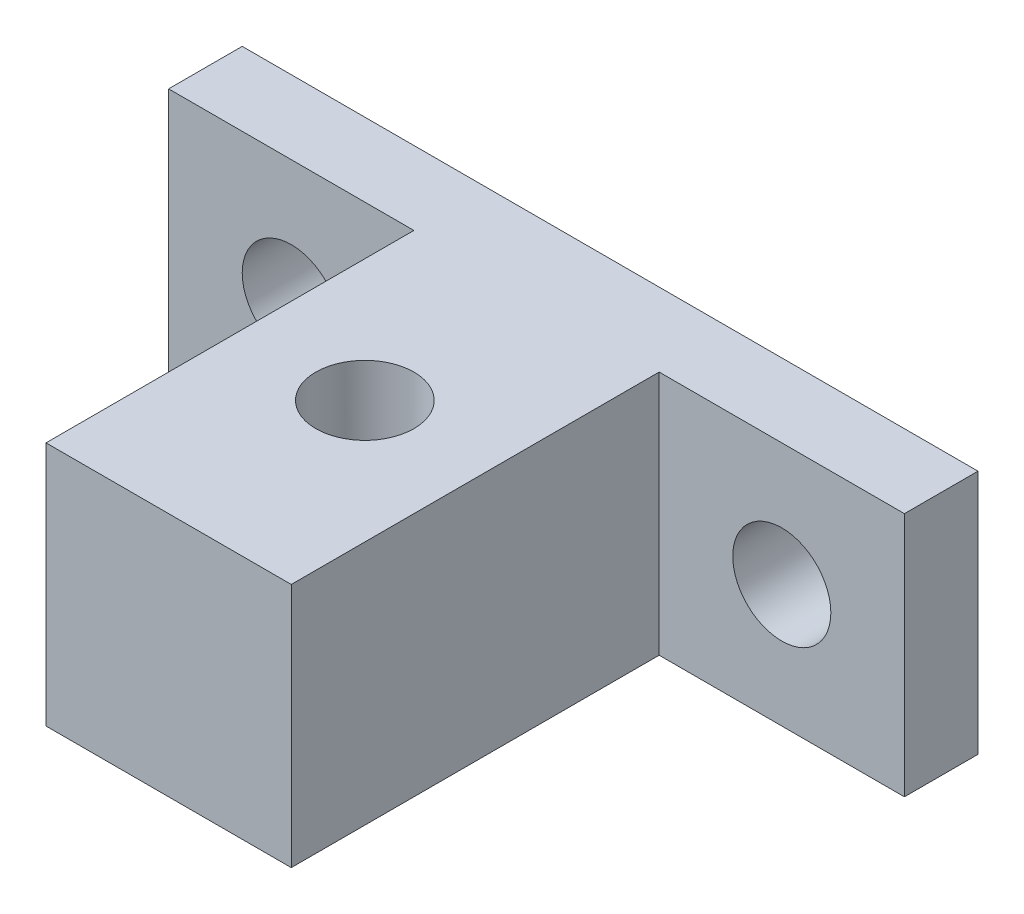
SolidWorks part; units mm, degrees
ref_plane "Front Plane" through (0, 0, 0) normal (0, 0, 1) x (1, 0, 0)
ref_plane "Top Plane" through (0, 0, 0) normal (0, 1, 0) x (1, 0, 0)
ref_plane "Right Plane" through (0, 0, 0) normal (1, 0, 0) x (0, 0, -1)
sketch "Sketch1" plane through (0, 0, 0) normal (0, 0, 1) x (1, 0, 0)
  line L0 (163.3569, -3.3) -> (103.3569, -3.3) construction
  line L1 (25, -3.3) -> (-5, -3.3)
  line L2 (25, -3.3) -> (25, -13.3)
  line L3 (25, -13.3) -> (-5, -13.3)
  line L4 (-5, -3.3) -> (-5, -13.3)
  line L5 (25, -3.3) -> (-5, -13.3) construction
  line L6 (25, -13.3) -> (-5, -3.3) construction
  line L7 (25, -8.3) -> (-5, -8.3) construction
  line L8 (10, -13.3) -> (10, -3.3) construction
  circle A0 centre (20, -8.3) radius 2
  circle A1 centre (0, -8.3) radius 2
  dimension "D3" = 4
  dimension "D4" = 10
  dimension "D1" = 10
  dimension "D2" = 30
extrude "Boss-Extrude1" add sketch "Sketch1" along normal blind 3
sketch "Sketch2" plane through (0, 0, 3) normal (0, 0, 1) x (1, 0, 0)
  line L0 (25, -3.3) -> (-5, -3.3) construction
  line L1 (15, -3.3) -> (5, -3.3)
  line L2 (15, -3.3) -> (15, -13.3)
  line L3 (15, -13.3) -> (5, -13.3)
  line L4 (5, -3.3) -> (5, -13.3)
  line L5 (15, -3.3) -> (5, -13.3) construction
  line L6 (15, -13.3) -> (5, -3.3) construction
  line L7 (-5, -13.3) -> (25, -13.3) construction
  line L9 (-5, -3.3) -> (-5, -13.3) construction
  line L10 (25, -13.3) -> (25, -3.3) construction
  point P4 (10, -8.3)
  dimension "D1" = 10
  dimension "D2" = 10
extrude "Boss-Extrude2" add sketch "Sketch2" along normal blind 15
sketch "Sketch3" plane through (0, -3.3, 0) normal (0, 1, 0) x (1, 0, 0)
  line L0 (5, -18) -> (5, -3) construction
  line L1 (10, -6.074) -> (6.6, -8.037)
  line L2 (6.6, -8.037) -> (6.6, -11.963)
  line L3 (6.6, -11.963) -> (10, -13.926)
  line L4 (10, -13.926) -> (13.4, -11.963)
  line L5 (13.4, -11.963) -> (13.4, -8.037)
  line L6 (13.4, -8.037) -> (10, -6.074)
  line L7 (25, 0) -> (-5, 0) construction
  circle A0 centre (10, -10) radius 3.4 construction
  circle A1 centre (10, -10) radius 2
  dimension "D3" = 10
  dimension "D4" = 4
  dimension "D1" = 6.8
  dimension "D2" = 5
extrude "Cut-Extrude1" cut sketch "Sketch3" along normal blind 5 from surface starting at face at (10, -13.3, 6)
extrude "Cut-Extrude2" cut sketch "Sketch3<2>" against normal through all both and the other way through all contours A1 region at (10, -3.3, 10)
sketch "Sketch3<2>" plane through (0, -3.3, 0) normal (0, 1, 0) x (1, 0, 0) same geometry as "Sketch3"
